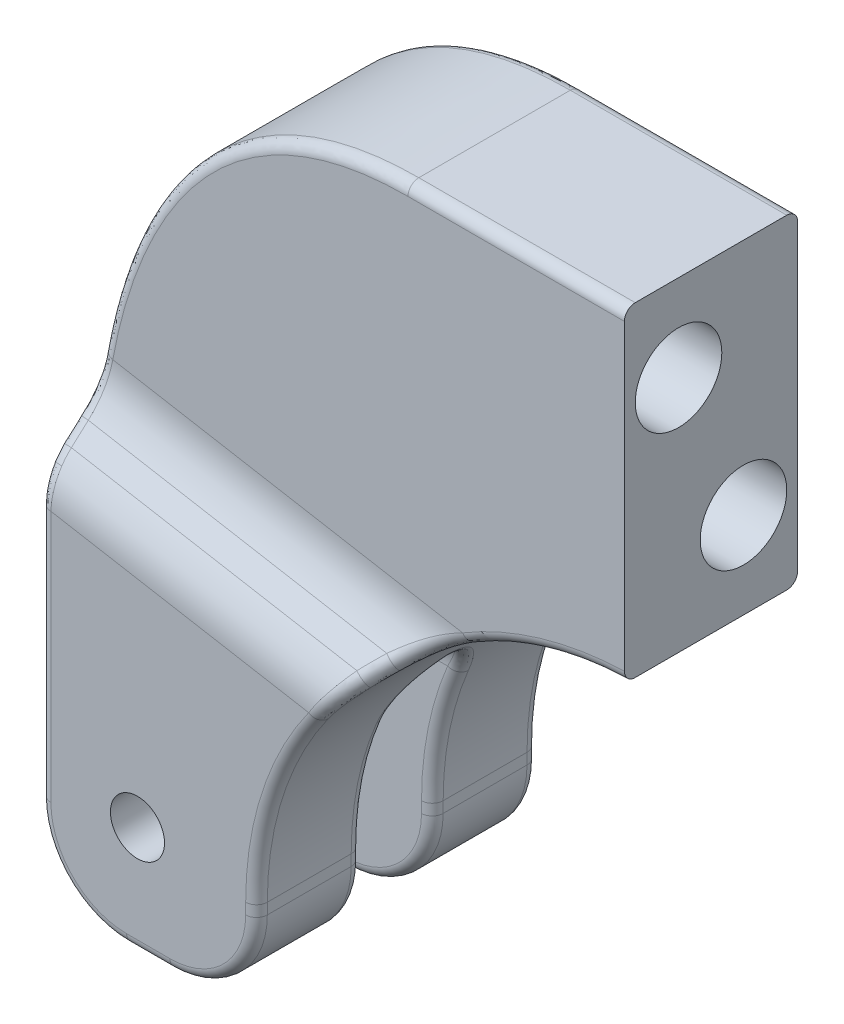
SolidWorks part; units mm, degrees
ref_plane "Płaszczyzna przednia" through (0, 0, 0) normal (0, 0, 1) x (1, 0, 0)
ref_plane "Płaszczyzna górna" through (0, 0, 0) normal (0, 1, 0) x (1, 0, 0)
ref_plane "Płaszczyzna prawa" through (0, 0, 0) normal (1, 0, 0) x (0, 0, -1)
sketch "Szkic1" plane through (0, 0, 0) normal (0, 0, 1) x (1, 0, 0)
  line L0 (0, 0) -> (0, 30)
  line L1 (0, 30) -> (-20, 30)
  line L5 (-29, 0) -> (0, 0)
  line L6 (-49, -5) -> (-49, -39)
  line L7 (-49, -39) -> (-29, -39)
  line L8 (-29, -39) -> (-29, 0)
  spline S0 degree 3 poles (-49, -5) (-49, 3.6363) (-44.6762, 30) (-20, 30) knots 0 0 0 0 1 1 1 1
  dimension "D5" = 69
  dimension "D1" = 20
  dimension "D2" = 49
  dimension "D3" = 35
  dimension "D4" = 30
  dimension "D6" = 20
extrude "Dodanie-wyciągnięcie1" add sketch "Szkic1" along normal mid plane 16
fillet "Zaokrąglenie5" radius 30 1 edges at (-29, 0, 0)
sketch "Szkic9" plane through (0, 0, -8) normal (0, 0, -1) x (-1, 0, 0)
  line L0 (49, -5) -> (49, -39) construction
  line L1 (49, -39) -> (29, -39) construction
  line L3 (49, -5) -> (49, -39)
  line L4 (49, -39) -> (29, -39)
  line L6 (49, -5) -> (21.2756, -9.8886)
  line L7 (29, -39) -> (29, -29.9833) construction
  line L8 (29, -39) -> (29, -29.9833)
  arc A0 (29, -29.9833) -> (0, 0) centre (-1, -29.9833) ccw construction
  arc A1 (29, -29.9833) -> (0, 0) centre (-1, -29.9833) ccw
  point P2 (37.0526, -6.0511)
  point P4 (0, 0)
  line M2 (29, -29.9833) -> (29, -39)
  line M3 (29, -39) -> (49, -39)
  line M4 (49, -39) -> (49, -5)
  arc M12 (0, 0) -> (29, -29.9833) centre (-1, -29.9833) cw
  dimension "D1" = 10
extrude "Dodanie-wyciągnięcie2" add sketch "Szkic9" along normal blind 5 contours L6 M4 M12 M2 M3 region at (-38.2186, -22.2, -8)
mirror "Lustro3" about plane through (0, 0, 0) normal (0, 0, 1) of "Dodanie-wyciągnięcie2"
chamfer "Sfazowanie1" distance 5 angle 45 2 edges at (-35.1378, -7.4443, -8) (-35.1378, -7.4443, 8)
sketch "Szkic2" plane through (0, -39, 0) normal (0, -1, 0) x (-1, 0, 0)
  line L1 (49, -3.25) -> (19, -3.25)
  line L2 (49, -3.25) -> (49, 3.25)
  line L3 (49, 3.25) -> (19, 3.25)
  line L4 (19, -3.25) -> (19, 3.25)
  line L6 (49, -13) -> (49, 13) construction
  point P6 (19, 0)
  dimension "D1" = 6.5
  dimension "D2" = 30
extrude "Wytnij-wyciągnięcie1" cut sketch "Szkic2" against normal blind 25
hole_wizard "Otwory ustalające Ø5.0mm1" positions "Szkic3" profile "Szkic5" hole size "Ø5.0" standard "Ansi Metric" end condition through all
sketch "Szkic3" plane through (0, 0, 13) normal (0, 0, 1) x (1, 0, 0)
  line L4 (-29, -39) -> (-49, -39) construction
  line L5 (-49, -39) -> (-49, -5) construction
  point P0 (-40, -29)
  point P17 (0, 0)
  point P18 (0, 0)
  dimension "D1" = 9
  dimension "D2" = 10
sketch "Szkic5" plane through (-40, -29, 13) normal (1, 0, 0) x (0, -1, 0)
  line L0 (0, 0) -> (0, 26)
  line L1 (0, 26) -> (2.5, 26)
  line L2 (2.5, 26) -> (2.5, 0)
  line L5 (2.5, 0) -> (0, 0)
  line L11 (0, -6.35) -> (0, 107.95) construction
  dimension "Średnica otworu na wylot" = 5
  dimension "Głębokość otworu na wylot" = 26
fillet "Zaokrąglenie1" radius 8 2 edges at (-29, -39, -8.125) (-49, -39, -8.125)
hole_wizard "Otwory ustalające Ø6.0mm2" positions "Szkic6" profile "Szkic7" hole size "Ø6.0" standard "Ansi Metric"
sketch "Szkic6" plane through (16, -185.3495, -49.25) normal (1, 0, 0) x (0, -1, 0)
  line L3 (-185.3495, -41.25) -> (-215.3495, -41.25)
  line L5 (-215.3495, -57.25) -> (-215.3495, -41.25)
  point P0 (-193.3495, -46.25)
  point P2 (-207.3495, -52.25)
sketch "Szkic7" plane through (16, 8, -3) normal (0, 1, 0) x (0, 0, -1)
  line L0 (0, 0) -> (0, 33.8026)
  line L1 (0, 33.8026) -> (3, 32)
  line L2 (3, 32) -> (3, 0)
  line L3 (3, 0) -> (0, 0)
  line L4 (0, 33.8026) -> (-3, 32) construction
  line L5 (0, -6.35) -> (0, 107.95) construction
  dimension "Średnica otworu" = 6
  dimension "Głębokość otworu" = 32
  dimension "Kąt wiertła" = 118
sketch "Szkic8" plane through (0, 0, 0) normal (1, 0, 0) x (0, 0, -1)
  circle A0 centre (3, 8) radius 3 construction
  circle A1 centre (-3, 22) radius 3 construction
  circle A2 centre (3, 8) radius 3 construction
  circle A3 centre (-3, 22) radius 3 construction
  circle A4 centre (3, 8) radius 4
  circle A5 centre (-3, 22) radius 4
  dimension "D1" = 8
extrude "Wytnij-wyciągnięcie2" cut sketch "Szkic8" against normal up to vertex (17.8026 mm away) up to point (-17.8026, 8, -3)
fillet "Zaokrąglenie8" radius 4 2 edges at (-36.6938, -14, -3.25) (-36.6938, -14, 3.25)
fillet "Zaokrąglenie9" radius 6 4 edges at (-32.5926, -2.8159, -8) (-35.1378, -7.4443, -13) (-35.1378, -7.4443, 13) (-32.5926, -2.8159, 8)
fillet "Zaokrąglenie7" radius 1 48 edges at (-49, -19.2618, -13) (-46.6569, -36.6569, -13) (-39, -39, -13) (-31.3431, -36.6569, -13) (-29, -30.4917, -13) (-49, -19.2618, 13) (-46.6569, -36.6569, 13) (-39, -39, 13) (-31.3431, -36.6569, 13) (-29, -30.4917, 13) (-27.4822, -20.5618, -13) (-27.4822, -20.5618, 13) (-6.9236, -1.0486, -8) (-16.219, -5.4169, -8.4193) (-19.111, -7.7225, -10.4909) (-21.4761, -10.1132, -12.5705) (-10, 30, -8) (-48.5758, 0.5179, -8.3352) (-49, -6.2325, -12.8637) (-6.9236, -1.0486, 8) (-16.6644, -5.7353, 8.5899) (-19.111, -7.7225, 10.4909) (-21.6667, -10.3309, 12.6633) (-10, 30, 8) (-48.6586, -0.1012, 8.5934) (-49, -6.2325, 12.8637) (-25.2674, -15.4911, -2.3653) (-49, -15.4505, -2.3322) (-49, -15.4505, 2.3322) (-25.1602, -15.2986, 2.2) (-28.369, -23.8629, 3.25) (-29, -30.4917, 3.25) (-31.3431, -36.6569, 3.25) (-39, -39, 3.25) (-46.6569, -36.6569, 3.25) (-29, -30.4917, -3.25) (-31.3431, -36.6569, -3.25) (-39, -39, -3.25) (-46.6569, -36.6569, -3.25) (-49, -24.5, -3.25) (-28.369, -23.8629, -3.25) (-49, -24.5, 3.25)
